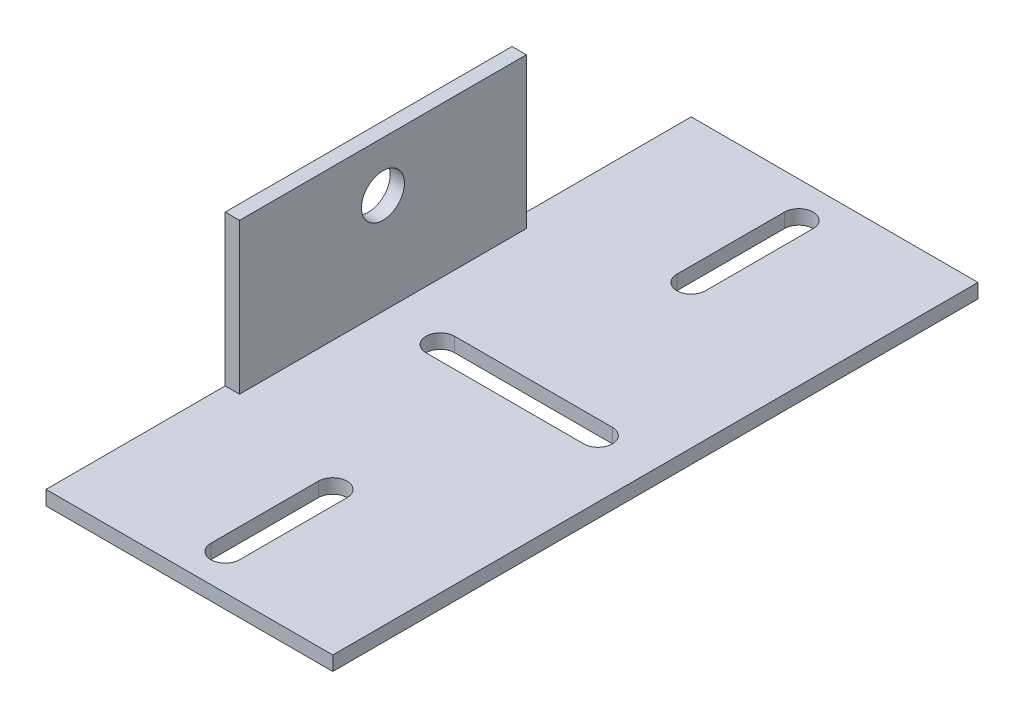
SolidWorks part; units mm, degrees
ref_plane "Спереди" through (0, 0, 0) normal (0, 0, 1) x (1, 0, 0)
ref_plane "Сверху" through (0, 0, 0) normal (0, 1, 0) x (1, 0, 0)
ref_plane "Справа" through (0, 0, 0) normal (1, 0, 0) x (0, 0, -1)
sketch "Эскиз2" plane through (0, 0, 0) normal (0, 0, 1) x (1, 0, 0)
  line L0 (0, 23) -> (0, 0)
  line L1 (0, 0) -> (40, 0)
extrude "Вытянуть-Тонкостенный1" add sketch "Эскиз2" along normal blind 90 thin thin type one direction reverse wall 2
sketch "Эскиз3" plane through (0, 2, 0) normal (0, 1, 0) x (1, 0, 0)
  line L0 (32, -43) -> (10, -43)
  line L1 (32, -47) -> (10, -47)
  line L2 (18, -5) -> (18, -20)
  line L3 (22, -5) -> (22, -20)
  line L4 (40, -45) -> (2, -45) construction
  line L5 (40, -90) -> (40, 0) construction
  line L6 (2, -90) -> (2, 0) construction
  line L7 (22, -85) -> (22, -70)
  line L8 (18, -85) -> (18, -70)
  arc A0 (32, -43) -> (32, -47) centre (32, -45) cw
  arc A1 (10, -43) -> (10, -47) centre (10, -45) ccw
  arc A2 (18, -5) -> (22, -5) centre (20, -5) cw
  arc A3 (18, -20) -> (22, -20) centre (20, -20) ccw
  arc A4 (18, -70) -> (22, -70) centre (20, -70) cw
  arc A5 (18, -85) -> (22, -85) centre (20, -85) ccw
  dimension "D1" = 20
extrude "Вырез-Вытянуть1" cut sketch "Эскиз3" against normal blind 10
sketch "Эскиз4" plane through (0, 0, 0) normal (-1, 0, 0) x (0, 0, 1)
  line L0 (45, 23) -> (45, 0) construction
  line L1 (90, 23) -> (0, 23) construction
  circle A0 centre (45, 16) radius 3
extrude "Вырез-Вытянуть2" cut sketch "Эскиз4" against normal blind 10
sketch "Эскиз5" plane through (0, 0, 0) normal (-1, 0, 0) x (0, 0, 1)
  line L0 (45, 23) -> (45, -0.8996) construction
  line L1 (0, 23) -> (25, 23)
  line L2 (0, 23) -> (0, 2)
  line L3 (0, 2) -> (25, 2)
  line L4 (25, 23) -> (25, 2)
  line L5 (90, 23) -> (0, 23) construction
  line L6 (65, 23) -> (65, 2)
  line L7 (90, 2) -> (65, 2)
  line L8 (90, 23) -> (90, 2)
  line L9 (90, 23) -> (65, 23)
extrude "Вырез-Вытянуть3" cut sketch "Эскиз5" against normal blind 10
